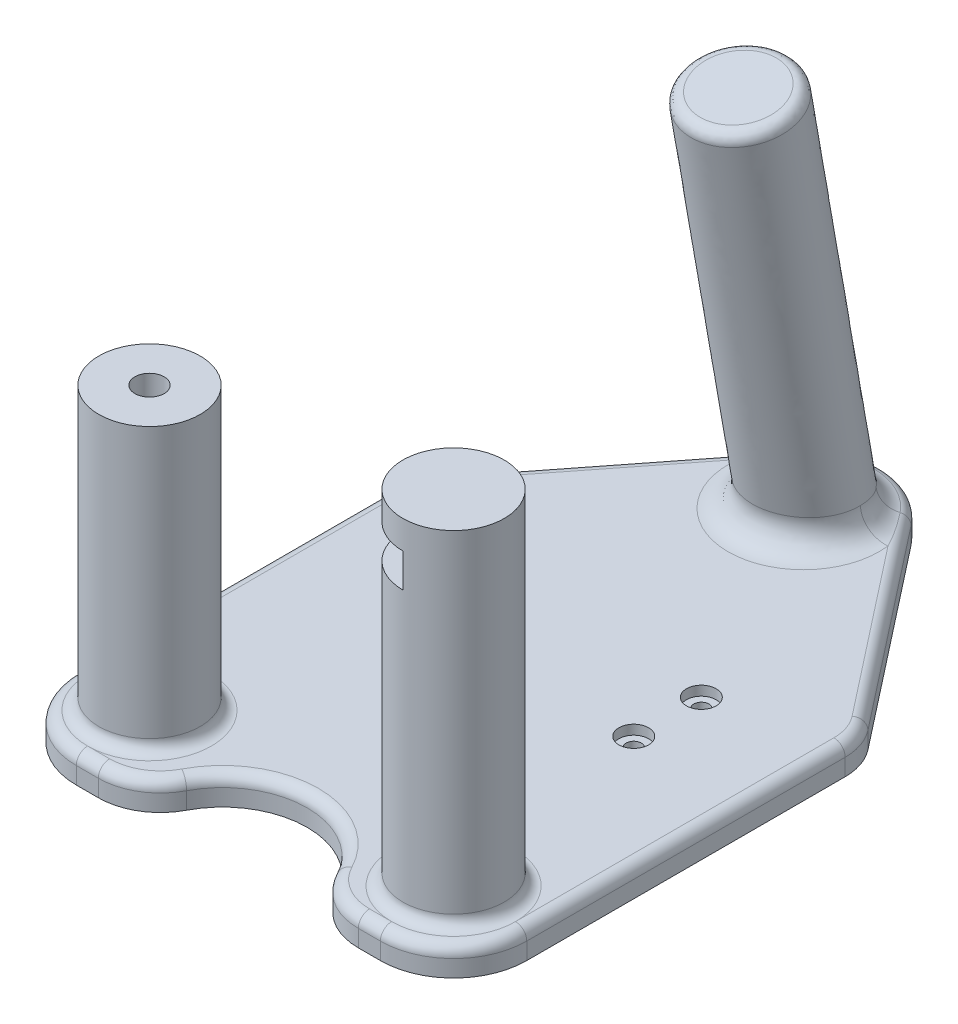
SolidWorks part; units mm, degrees
note: The reader was unsure of these and kept them because the rebuilt part matched: shared geometry of "Sketch1<4>".
ref_plane "Front Plane" through (0, 0, 0) normal (0, 0, 1) x (1, 0, 0)
ref_plane "Top Plane" through (0, 0, 0) normal (0, 1, 0) x (1, 0, 0)
ref_plane "Right Plane" through (0, 0, 0) normal (1, 0, 0) x (0, 0, -1)
sketch "Sketch1" plane through (0, 0, 0) normal (0, 1, 0) x (1, 0, 0)
  line L0 (-34.29, 0) -> (34.29, 0) construction
  line L1 (0, 0) -> (0, 114.3) construction
  line L2 (-50.8, 0) -> (-50.8, 76.2)
  line L3 (-50.8, 76.2) -> (-12.9994, 124.4782)
  line L4 (-34.29, -16.51) -> (34.29, -16.51)
  line L5 (12.9994, 124.4782) -> (50.8, 76.2)
  line L6 (50.8, 76.2) -> (50.8, 0)
  circle A0 centre (-34.29, 0) radius 11.43
  circle A1 centre (34.29, 0) radius 11.43
  circle A2 centre (0, 114.3) radius 11.43
  arc A3 (12.9994, 124.4782) -> (-12.9994, 124.4782) centre (0, 114.3) ccw
  arc A4 (-50.8, 0) -> (-34.29, -16.51) centre (-34.29, 0) ccw
  arc A5 (34.29, -16.51) -> (50.8, 0) centre (34.29, 0) ccw
  circle A6 centre (0, 114.3) radius 16.51 construction
  circle A7 centre (-34.29, 0) radius 16.51 construction
  circle A8 centre (34.29, 0) radius 16.51 construction
  point P3 (0, 0)
  dimension "D2" = 22.86
  dimension "D3" = 22.86
  dimension "D1" = 68.58
  dimension "D4" = 114.3
  dimension "D6" = 76.2
  dimension "D5" = 5.08
extrude "Boss-Extrude1" add sketch "Sketch1" against normal blind 6.35 contours A0 | A1 | L4 A5 L6 L5 A3 L3 L2 A4 A0 A1 A2 | A2
fillet "Fillet1" radius 12.7 2 edges at (50.8, -3.175, -76.2) (-50.8, -3.175, -76.2)
extrude "Boss-Extrude2" add sketch "Sketch1<4>" along normal blind 63.5 contours A0 | A1
sketch "Sketch1<4>" plane through (0, 0, 0) normal (0, 1, 0) x (1, 0, 0) same geometry as "Sketch1"
sketch "Sketch8" plane through (0, 0, 0) normal (0, 1, 0) x (1, 0, 0)
  line L0 (0, 102.87) -> (-29.9181, 102.87)
  line L1 (0, 102.87) -> (29.9181, 102.87)
  line L5 (50.8, 0) -> (50.8, 71.8196)
  line L6 (48.0995, 79.649) -> (12.9994, 124.4782)
  line L7 (-12.9994, 124.4782) -> (-48.0995, 79.649)
  line L8 (-50.8, 71.8196) -> (-50.8, 0)
  line L9 (-34.29, -16.51) -> (34.29, -16.51)
  line L10 (50.8, 0) -> (50.8, 71.8196)
  line L11 (48.0995, 79.649) -> (12.9994, 124.4782)
  line L12 (-12.9994, 124.4782) -> (-48.0995, 79.649)
  line L13 (-50.8, 71.8196) -> (-50.8, 0)
  line L14 (-34.29, -16.51) -> (34.29, -16.51)
  circle A0 centre (0, 114.3) radius 11.43 construction
  arc A5 (50.8, 71.8196) -> (48.0995, 79.649) centre (38.1, 71.8196) ccw
  arc A6 (12.9994, 124.4782) -> (-12.9994, 124.4782) centre (0, 114.3) ccw
  arc A7 (-48.0995, 79.649) -> (-50.8, 71.8196) centre (-38.1, 71.8196) ccw
  arc A8 (-50.8, 0) -> (-34.29, -16.51) centre (-34.29, 0) ccw
  arc A9 (34.29, -16.51) -> (50.8, 0) centre (34.29, 0) ccw
  arc A10 (50.8, 71.8196) -> (48.0995, 79.649) centre (38.1, 71.8196) ccw
  arc A11 (12.9994, 124.4782) -> (-12.9994, 124.4782) centre (0, 114.3) ccw
  arc A12 (-48.0995, 79.649) -> (-50.8, 71.8196) centre (-38.1, 71.8196) ccw
  arc A13 (-50.8, 0) -> (-34.29, -16.51) centre (-34.29, 0) ccw
  arc A14 (34.29, -16.51) -> (50.8, 0) centre (34.29, 0) ccw
  dimension "D2" = 22.86
  dimension "D1" = 0
ref_plane "Plane1" through (0, -17.5918, -3.1019) normal (0, 0.9848, 0.1736) x (1, 0, 0)
sketch "Sketch9" plane through (0, -17.5918, -3.1019) normal (0, 0.9848, 0.1736) x (1, 0, 0)
  ellipse E0 centre (0, 112.5635) end of major axis (11.43, 112.5635) minor radius 11.2564 construction
  ellipse E1 centre (0, 112.5635) end of major axis (11.43, 112.5635) minor radius 11.2564
extrude "Boss-Extrude10" add sketch "Sketch9" along normal blind 88.9 and the other way up to surface other way up to face at (-34.29, 0, 11.43)
sketch "Sketch2" plane through (0, 63.5, 0) normal (0, 1, 0) x (1, 0, 0)
  line L0 (34.29, -11.43) -> (34.29, 0)
  circle A1 centre (34.29, 0) radius 11.43
  circle A2 centre (34.29, 0) radius 11.43
  circle A3 centre (22.86, 0) radius 11.43 construction
  arc A4 (34.29, 0) -> (28.575, 9.8987) centre (22.86, 0) ccw
  dimension "D1" = 0
extrude "Boss-Extrude4" add sketch "Sketch2" along normal blind 7.62
sketch "Sketch3" plane through (0, 71.12, 0) normal (0, 1, 0) x (1, 0, 0)
  circle A0 centre (34.29, 0) radius 11.43
  arc A2 (34.29, -11.43) -> (28.575, 9.8987) centre (34.29, 0) ccw construction
extrude "Boss-Extrude5" add sketch "Sketch3" along normal blind 6.35
sketch "Sketch6" plane through (0, 63.5, 0) normal (0, 1, 0) x (1, 0, 0)
  circle A1 centre (-34.29, 0) radius 11.43
  circle A2 centre (-34.29, 0) radius 11.43
  circle A3 centre (-34.29, 0) radius 6.35
  dimension "D2" = 12.7
  dimension "D1" = 0
extrude "Boss-Extrude8" [suppressed] add sketch "Sketch6" along normal up to surface (7.62 mm away) contours A3
sketch "Sketch7" [suppressed] plane through (0, 71.12, 0) normal (0, 1, 0) x (1, 0, 0)
  circle A0 centre (-34.29, 0) radius 11.43 construction
  circle A1 centre (-34.29, 0) radius 11.43
extrude "Boss-Extrude9" [suppressed] add sketch "Sketch7" along normal up to surface (10.16 mm away)
fillet "Fillet3" [suppressed] radius 1.27
other "Move Face1" [suppressed] parameters "D1"=0.254
sketch "Sketch10" plane through (0, 0, 0) normal (0, 1, 0) x (1, 0, 0)
  line L0 (-34.29, -16.51) -> (34.29, -16.51) construction
  line L1 (-19.05, -16.51) -> (-34.29, -16.51) construction
  line L2 (19.05, -16.51) -> (34.29, -16.51) construction
  line L3 (0, 1.27) -> (0, -16.51) construction
  line L4 (-19.05, -16.51) -> (19.05, -16.51)
  arc A0 (19.05, -16.51) -> (-19.05, -16.51) centre (0, -17.8254) ccw
  dimension "D1" = 17.78
  dimension "D2" = 38.1
extrude "Cut-Extrude1" cut sketch "Sketch10" against normal blind 88.9
fillet "Fillet7" radius 13.97 2 edges at (19.05, -3.175, 16.51) (-19.05, -3.175, 16.51)
fillet "Fillet8" radius 2.54 10 edges at (0, 0, -1.27) (-31.8051, 0, 16.51) (31.8051, 0, 16.51) (45.9643, 0, 11.6743) (50.8, 0, -35.9098) (30.5495, 0, -102.0636) (0, 0, -130.81) (-30.5495, 0, -102.0636) (-50.8, 0, -35.9098) (-45.9643, 0, 11.6743) tangent propagation no
fillet "Fillet9" radius 2.54 1 edges at (11.43, 89.5041, -98.518)
fillet "Fillet10" radius 5.588 1 edges at (-11.2376, 0, -112.2114)
sketch "Sketch11" plane through (0, 0, 0) normal (0, 1, 0) x (1, 0, 0)
  line L0 (0, 130.81) -> (0, -16.51) construction
  line L1 (-34.29, -16.51) -> (34.29, -16.51) construction
  line L2 (0, 57.15) -> (-50.8, 57.15) construction
  line L3 (-50.8, 71.8196) -> (-50.8, 0) construction
  line L4 (0, 57.15) -> (50.8, 57.15) construction
  line L5 (50.8, 0) -> (50.8, 71.8196) construction
  line L6 (-18.6214, 57.15) -> (19.4786, 57.15) construction
  line L7 (-18.6214, 57.15) -> (19.4786, 57.15) construction
  line L9 (58.801, 43.307) -> (-58.801, 43.307) construction
  line L10 (58.801, 43.307) -> (58.801, 70.993) construction
  line L11 (58.801, 70.993) -> (-58.801, 70.993) construction
  line L12 (-58.801, 43.307) -> (-58.801, 70.993) construction
  line L13 (58.801, 43.307) -> (-58.801, 70.993) construction
  line L14 (58.801, 70.993) -> (-58.801, 43.307) construction
  line L15 (25.4, 49.53) -> (-25.4, 49.53) construction
  line L16 (25.4, 49.53) -> (25.4, 64.77) construction
  line L17 (25.4, 64.77) -> (-25.4, 64.77) construction
  line L18 (-25.4, 49.53) -> (-25.4, 64.77) construction
  line L19 (25.4, 49.53) -> (-25.4, 64.77) construction
  line L20 (25.4, 64.77) -> (-25.4, 49.53) construction
  arc A0 (12.9994, 124.4782) -> (-12.9994, 124.4782) centre (0, 114.3) ccw construction
  circle A3 centre (-25.4, 64.77) radius 1.6
  circle A4 centre (-25.4, 49.53) radius 1.6
  circle A5 centre (25.4, 49.53) radius 1.6
  circle A6 centre (25.4, 64.77) radius 1.6
  dimension "D1" = 117.602
  dimension "D5" = 3.2
  dimension "D2" = 50.8
  dimension "D3" = 27.686
  dimension "D4" = 15.24
hole_wizard "CBORE for M3 SBHCS1" positions "3DSketch1" profile "Sketch12" counterbore size "M3" standard "ANSI Metric"
sketch3d "3DSketch1"
  point P0 (-25.4, 0, -64.77)
  point P3 (-25.4, 0, -49.53)
  point P6 (25.4, 0, -64.77)
  point P9 (25.4, 0, -49.53)
sketch "Sketch12" plane through (-25.4, 0, -64.77) normal (1, 0, 0) x (0, 0, 1)
  line L0 (0, 0) -> (0, 7.3715)
  line L1 (0, 7.3715) -> (1.7, 6.35)
  line L2 (1.7, 6.35) -> (1.7, 1.65)
  line L3 (1.7, 1.65) -> (3.35, 1.65)
  line L4 (3.35, 1.65) -> (3.35, 0)
  line L5 (3.35, 0) -> (0, 0)
  line L10 (0, 7.3715) -> (-1.7, 6.35) construction
  line L11 (0, -6.35) -> (0, 107.95) construction
  dimension "Hole Dia." = 3.4
  dimension "Hole Depth" = 6.35
  dimension "C'Bore Dia." = 6.7
  dimension "C'Bore Depth" = 1.65
  dimension "Drill Angle" = 118
other "Move Face2" flip direction yes face at (25.4, -1.65, -63.07) face at (25.4, -1.65, -47.83) face at (-25.4, -1.65, -47.83) face at (-25.4, -1.65, -63.07) parameters "D1"=0.508
fillet "Fillet11" radius 2.54 2 edges at (34.29, 0, 11.43) (-34.29, 0, 11.43)
sketch "Sketch13" plane through (0, 63.5, 0) normal (0, 1, 0) x (1, 0, 0)
  circle A0 centre (-34.29, 0) radius 3.3
  circle A1 centre (-34.29, 0) radius 11.43
  circle A2 centre (-34.29, 0) radius 11.43
  dimension "D2" = 6.6
  dimension "D1" = 0
extrude "Cut-Extrude2" cut sketch "Sketch13" against normal blind 14 contours A0
